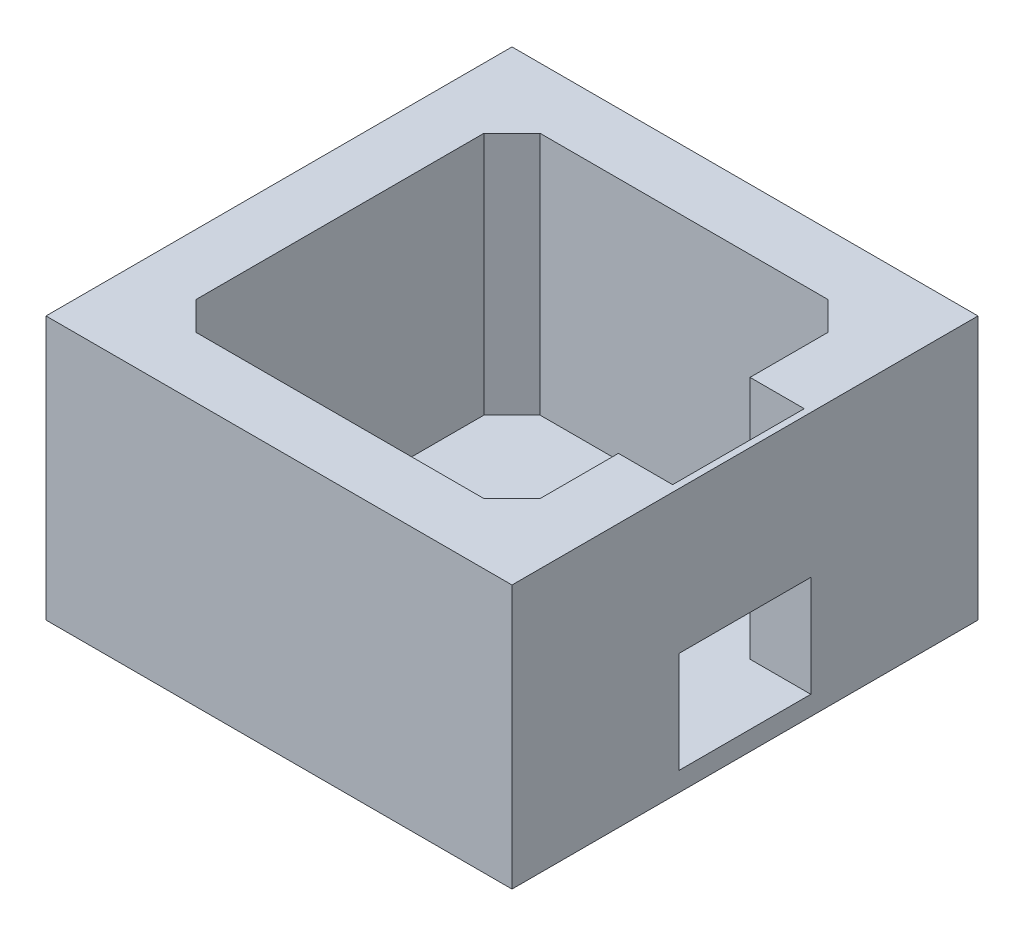
SolidWorks part; units mm, degrees
ref_plane "Front Plane" through (0, 0, 0) normal (0, 0, 1) x (1, 0, 0)
ref_plane "Top Plane" through (0, 0, 0) normal (0, 1, 0) x (1, 0, 0)
ref_plane "Right Plane" through (0, 0, 0) normal (1, 0, 0) x (0, 0, -1)
sketch "Sketch1" plane through (0, 0, 0) normal (0, 1, 0) x (1, 0, 0)
  line L1 (0, 0) -> (58.42, 0)
  line L2 (0, 0) -> (0, 58.42)
  line L3 (0, 58.42) -> (58.42, 58.42)
  line L4 (58.42, 0) -> (58.42, 58.42)
  dimension "D1" = 58.42
  dimension "D2" = 58.42
extrude "Boss-Extrude1" add sketch "Sketch1" along normal blind 33.02
sketch "Sketch2" plane through (0, 33.02, 0) normal (0, 1, 0) x (1, 0, 0)
  line L0 (11.1555, 50.8) -> (47.2645, 50.8)
  line L1 (47.2645, 50.8) -> (50.8, 47.2645)
  line L2 (50.8, 47.2645) -> (50.8, 37.46)
  line L3 (50.8, 11.1555) -> (47.2645, 7.62)
  line L4 (47.2645, 7.62) -> (11.1555, 7.62)
  line L5 (11.1555, 7.62) -> (7.62, 11.1555)
  line L6 (7.62, 11.1555) -> (7.62, 47.2645)
  line L7 (7.62, 47.2645) -> (11.1555, 50.8)
  line L8 (50.8, 20.96) -> (50.8, 11.1555)
  line L9 (50.8, 37.46) -> (57.6, 37.46)
  line L10 (50.8, 20.96) -> (57.6, 20.96)
  line L11 (57.6, 37.46) -> (57.6, 20.96)
  line L12 (58.42, 58.42) -> (0, 58.42) construction
  line L13 (0, 58.42) -> (0, 0) construction
  point P9 (7.62, 29.21)
  point P14 (57.6, 29.21)
  point P17 (29.21, 58.42)
  point P18 (29.21, 50.8)
  point P21 (0, 29.21)
  dimension "D1" = 5
  dimension "D2" = 43.18
  dimension "D3" = 135
  dimension "D4" = 135
  dimension "D5" = 135
  dimension "D6" = 43.18
  dimension "D7" = 16.5
  dimension "D8" = 6.8
extrude "Cut-Extrude1" cut sketch "Sketch2" against normal blind 30.6
sketch "Sketch3" plane through (58.42, 0, 0) normal (1, 0, 0) x (0, 0, -1)
  line L0 (20.96, 15.12) -> (37.46, 15.12)
  line L1 (20.96, 15.12) -> (20.96, 2.42)
  line L2 (20.96, 2.42) -> (37.46, 2.42)
  line L3 (37.46, 15.12) -> (37.46, 2.42)
  line L4 (0, 33.02) -> (58.42, 33.02) construction
  point P4 (29.21, 33.02)
  point P7 (29.21, 15.12)
  dimension "D1" = 16.5
  dimension "D2" = 12.7
  dimension "D3" = 30.6
extrude "Cut-Extrude2" cut sketch "Sketch3" against normal blind 30.6
